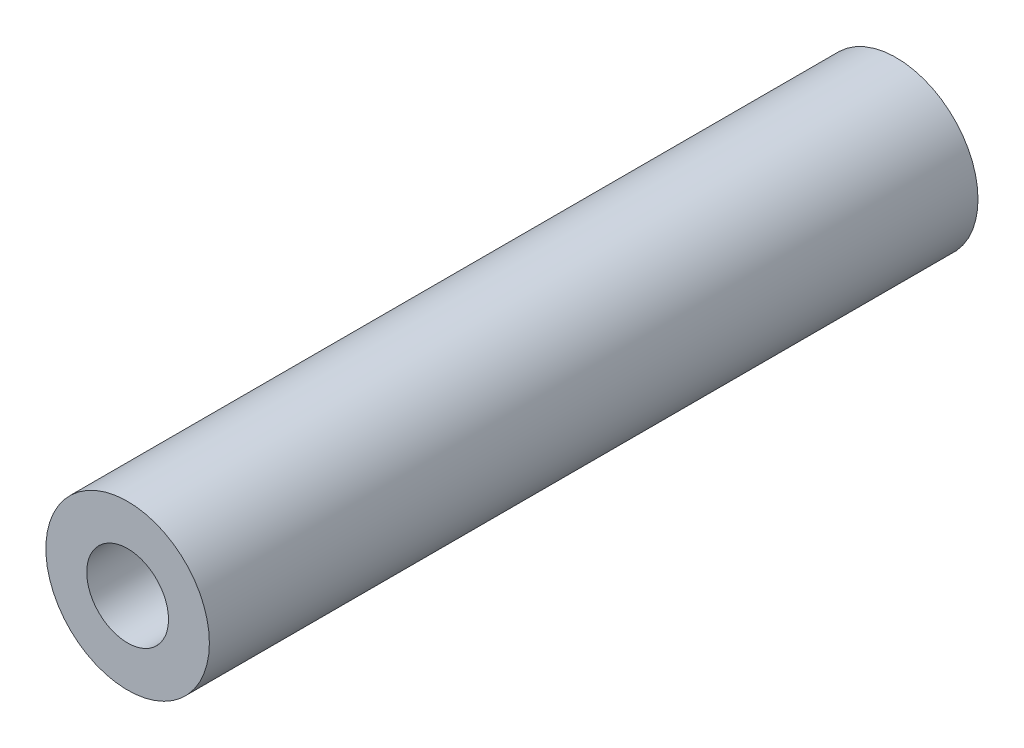
SolidWorks part; units mm, degrees
ref_plane "Front Plane" through (0, 0, 0) normal (0, 0, 1) x (1, 0, 0)
ref_plane "Top Plane" through (0, 0, 0) normal (0, 1, 0) x (1, 0, 0)
ref_plane "Right Plane" through (0, 0, 0) normal (1, 0, 0) x (0, 0, -1)
sketch "Sketch1" plane through (0, 0, 0) normal (0, 0, 1) x (1, 0, 0)
  circle A0 centre (0, 0) radius 5
  circle A1 centre (0, 0) radius 2.5
  dimension "D1" = 5
  dimension "D2" = 10
extrude "Boss-Extrude1" add sketch "Sketch1" along normal blind 47
